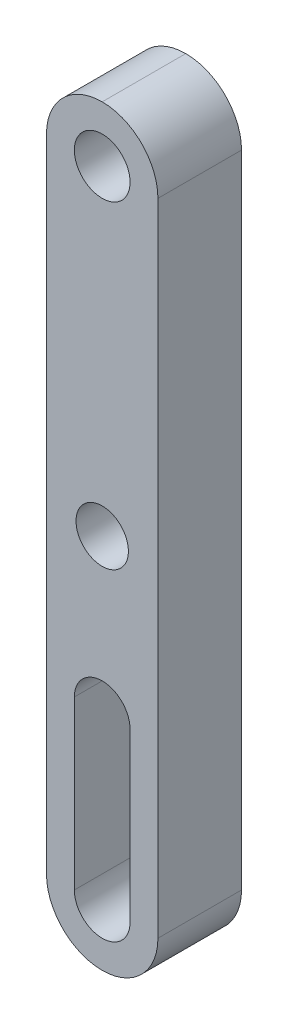
SolidWorks part; units mm, degrees
material "AISI Type A2 Tool Steel"
ref_plane "Front Plane" through (0, 0, 0) normal (0, 0, 1) x (1, 0, 0)
ref_plane "Top Plane" through (0, 0, 0) normal (0, 1, 0) x (1, 0, 0)
ref_plane "Right Plane" through (0, 0, 0) normal (1, 0, 0) x (0, 0, -1)
sketch "Sketch1" plane through (0, 0, 0) normal (0, 0, 1) x (1, 0, 0)
  line L0 (0, -2.6194) -> (0, 2.6194) construction
  line L1 (-3.175, 21.4312) -> (3.175, 21.4312)
  line L2 (-3.175, 21.4312) -> (-3.175, -21.4312)
  line L3 (-3.175, -21.4312) -> (3.175, -21.4312)
  line L4 (3.175, 21.4312) -> (3.175, -21.4312)
  line L5 (2.6194, 0) -> (-2.6194, 0) construction
  point P4 (0, 21.4312)
  point P7 (-3.175, 0)
  dimension "D1" = 6.35
  dimension "D2" = 42.8625
extrude "Boss-Extrude1" add sketch "Sketch1" along normal blind 4.7625
sketch "Sketch2" plane through (0, 0, 4.7625) normal (0, 0, 1) x (1, 0, 0)
  circle A0 centre (0, 0) radius 1.4922
  dimension "D1" = 2.9845
extrude "Cut-Extrude1" cut sketch "Sketch2" against normal through all
sketch "Sketch3" plane through (0, 0, 4.7625) normal (0, 0, 1) x (1, 0, 0)
  line L0 (0, -2.6194) -> (0, 2.6194) construction
  line L1 (2.6194, 0) -> (-2.6194, 0) construction
  line L2 (1.5875, -18.2562) -> (1.5875, -8.7312)
  line L3 (-1.5875, -18.2562) -> (-1.5875, -8.7312)
  circle A0 centre (0, 18.2562) radius 1.5875
  arc A1 (-1.5875, -18.2562) -> (1.5875, -18.2562) centre (0, -18.2562) ccw
  arc A2 (-1.5875, -8.7312) -> (1.5875, -8.7312) centre (0, -8.7312) cw
  dimension "D1" = 36.5125
  dimension "D3" = 3.175
  dimension "D4" = 3.175
  dimension "D5" = 9.525
  dimension "D2" = 18.2562
extrude "Cut-Extrude2" cut sketch "Sketch3" against normal through all
fillet "Fillet1" radius 3.175
